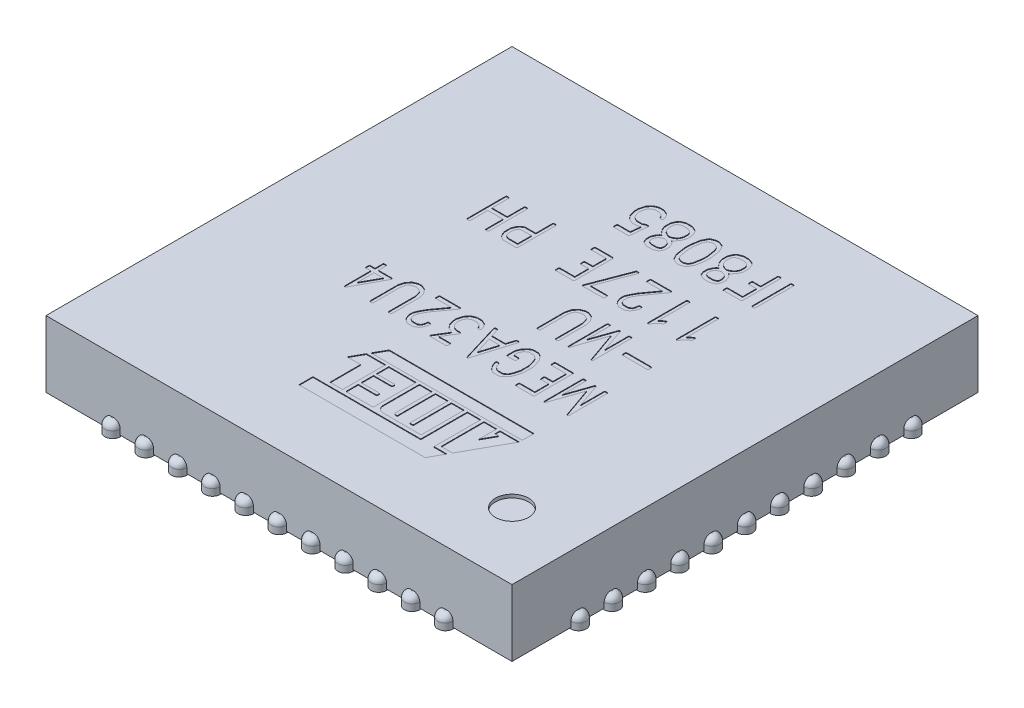
SolidWorks part; units mm, degrees
ref_plane "Front Plane" through (0, 0, 0) normal (0, 0, 1) x (1, 0, 0)
ref_plane "Top Plane" through (0, 0, 0) normal (0, 1, 0) x (1, 0, 0)
ref_plane "Right Plane" through (0, 0, 0) normal (1, 0, 0) x (0, 0, -1)
ref_plane "Plane1" through (0, 0, 0) normal (0, 1, 0) x (-1, 0, 0)
sketch "Sketch1" plane through (0, 0, 0) normal (0, 1, 0) x (-1, 0, 0)
  line L0 (-3.5, 3.5) -> (3.5, 3.5)
  line L1 (3.5, 3.5) -> (3.5, -3.5)
  line L2 (3.5, -3.5) -> (-3.5, -3.5)
  line L3 (-3.5, -3.5) -> (-3.5, 3.5)
  line L4 (55, 0) -> (-55, 0) construction
  line L5 (0, 55) -> (0, -55) construction
  dimension "D1" = 3.5
  dimension "D2" = 7
  dimension "D3" = 3.5
extrude "Boss-Extrude1" add sketch "Sketch1" along normal blind 1
ref_plane "Plane8" through (0, 0, 2.8) normal (0, 0, 1) x (1, 0, 0)
ref_plane "Plane10" through (0, -0.1, 0) normal (0, 1, 0) x (1, 0, 0)
ref_plane "Plane4" through (3.25, 0.6967, 3.35) normal (0, 1, 0) x (0, 0, -1)
ref_plane "Plane9" through (-2.8, 0, 0) normal (1, 0, 0) x (0, 0, -1)
sketch "Sketch4" plane through (0, 1, 0) normal (0, 1, 0) x (1, 0, 0)
  line L2 (3.5, -3.5) -> (3.5, 3.5) construction
  line L3 (-3.5, -3.5) -> (3.5, -3.5) construction
  circle A0 centre (2.5, -2.5) radius 0.25
  dimension "D2" = 0.5
  dimension "D1" = 1
  dimension "D3" = 1
extrude "Cut-Extrude1" cut sketch "Sketch4" against normal blind 0.05
sketch "Sketch8" plane through (0, 1, 0) normal (0, 1, 0) x (1, 0, 0)
  line L0 (-0.5975, -1.59) -> (-0.31, -1.59)
  line L1 (1.7, -1.545) -> (-0.5725, -1.545)
  line L2 (-0.4755, -1.37) -> (-0.5725, -1.545)
  line L3 (-0.26, -1.775) -> (0.005, -1.775)
  line L4 (-0.7, -1.775) -> (-0.5, -1.775)
  line L5 (-0.26, -1.82) -> (0.005, -1.82)
  line L6 (-0.26, -2.005) -> (0.005, -2.005)
  line L7 (-0.26, -2.05) -> (0.005, -2.05)
  line L8 (-0.7, -2.29) -> (0.92, -2.29)
  line L10 (-0.7, -2.5) -> (1.1956, -2.5)
  line L11 (1.7, -1.59) -> (1.3425, -2.235)
  line L12 (0.3, -2.235) -> (0.87, -2.235)
  line L13 (1.41, -1.59) -> (1.41, -1.665)
  line L14 (-0.4755, -1.37) -> (1.7, -1.37)
  line L15 (1.7, -1.37) -> (1.7, -1.545)
  line L16 (1.41, -1.665) -> (1.465, -1.665)
  line L17 (1.465, -1.665) -> (1.36, -1.8544)
  line L18 (1.36, -1.8544) -> (1.36, -1.59)
  line L21 (-0.31, -1.59) -> (-0.31, -2.235)
  line L22 (-0.26, -1.59) -> (-0.26, -2.235)
  line L23 (0.15, -1.59) -> (0.15, -2.235)
  line L24 (0.2, -1.59) -> (0.2, -2.135)
  line L25 (0.39, -1.59) -> (0.39, -2.135)
  line L26 (0.44, -1.59) -> (0.44, -2.165)
  line L27 (0.63, -1.59) -> (0.63, -2.155)
  line L28 (0.68, -1.59) -> (0.68, -2.155)
  line L29 (0.87, -1.59) -> (0.87, -2.235)
  line L30 (0.92, -1.59) -> (0.92, -2.29)
  line L31 (1.12, -1.59) -> (1.12, -2.29)
  line L32 (1.17, -1.59) -> (1.17, -2.235)
  line L33 (0.67, -2.165) -> (0.64, -2.165)
  line L34 (0.44, -2.165) -> (0.42, -2.165)
  line L35 (0.15, -2.235) -> (-0.26, -2.235)
  line L36 (-0.5, -1.775) -> (-0.5, -2.235)
  line L37 (-0.5975, -1.59) -> (-0.7, -1.775)
  line L38 (0.02, -1.79) -> (0.02, -1.805)
  line L39 (1.17, -2.235) -> (1.3425, -2.235)
  line L40 (1.12, -2.29) -> (1.312, -2.29)
  line L41 (-0.26, -1.59) -> (0.15, -1.59)
  line L42 (0.2, -1.59) -> (0.39, -1.59)
  line L43 (0.02, -2.02) -> (0.02, -2.035)
  line L45 (-0.31, -2.235) -> (-0.5, -2.235)
  line L46 (-0.7, -2.29) -> (-0.7, -2.5)
  line L47 (1.312, -2.29) -> (1.1956, -2.5)
  line L48 (0.44, -1.59) -> (0.63, -1.59)
  line L49 (0.68, -1.59) -> (0.87, -1.59)
  line L50 (0.92, -1.59) -> (1.12, -1.59)
  line L51 (1.17, -1.59) -> (1.36, -1.59)
  line L52 (1.41, -1.59) -> (1.7, -1.59)
  line L53 (3.5, -3.5) -> (3.5, 3.5) construction
  line L54 (-3.5, -3.5) -> (3.5, -3.5) construction
  arc A0 (0.3, -2.235) -> (0.2, -2.135) centre (0.3, -2.135) cw
  arc A1 (0.42, -2.165) -> (0.39, -2.135) centre (0.42, -2.135) cw
  arc A2 (0.67, -2.165) -> (0.68, -2.155) centre (0.67, -2.155) ccw
  arc A3 (0.63, -2.155) -> (0.64, -2.165) centre (0.64, -2.155) ccw
  arc A4 (0.005, -2.05) -> (0.02, -2.035) centre (0.005, -2.035) ccw
  arc A5 (0.02, -2.02) -> (0.005, -2.005) centre (0.005, -2.02) ccw
  arc A6 (0.005, -1.82) -> (0.02, -1.805) centre (0.005, -1.805) ccw
  arc A7 (0.02, -1.79) -> (0.005, -1.775) centre (0.005, -1.79) ccw
  point P76 (0.02, -2.005)
  dimension "D28" = 0.1
  dimension "D29" = 0.03
  dimension "D31" = 0.01
  dimension "D36" = 0.015
  dimension "D1" = 0.045
  dimension "D2" = 0.045
  dimension "D3" = 0.045
  dimension "D4" = 0.055
  dimension "D5" = 61
  dimension "D6" = 0.075
  dimension "D7" = 0.055
  dimension "D8" = 1.8
  dimension "D9" = 0.175
  dimension "D10" = 0.185
  dimension "D11" = 0.185
  dimension "D12" = 0.185
  dimension "D13" = 0.21
  dimension "D14" = 0.05
  dimension "D15" = 0.05
  dimension "D16" = 0.05
  dimension "D17" = 0.05
  dimension "D18" = 0.05
  dimension "D19" = 0.05
  dimension "D20" = 0.53
  dimension "D21" = 0.2
  dimension "D22" = 0.19
  dimension "D23" = 0.19
  dimension "D24" = 0.19
  dimension "D25" = 0.41
  dimension "D26" = 2.4
  dimension "D27" = 1
  dimension "D30" = 0.07
  dimension "D32" = 0.19
  dimension "D33" = 0.19
  dimension "D34" = 0.05
  dimension "D35" = 0.28
  dimension "D37" = 1.13
extrude "Cut-Extrude3" cut sketch "Sketch8" against normal blind 0.01 contours L15 L14 L2 L1 | A3 L27 L48 L26 L34 A1 L25 L42 L24 A0 L12 L29 L49 L28 A2 L33 | L50 L30 L8 L46 L10 L47 L40 L31 | L52 L13 L16 L17 L18 L51 L32 L39 L11 | A7 L38 A6 L5 L22 L6 A5 L43 A4 L7 L35 L23 L41 L3 | L45 L21 L0 L37 L4 L36 region at (-0.4366, 1, 1.8723) region at (0.5878, 1, 1.4581) region at (-0.0481, 1, 1.9125) region at (0.11, 1, 2.3121) region at (1.3588, 1, 1.8679) region at (0.5367, 1, 1.9163)
sketch "Sketch9" plane through (0, 1, 0) normal (0, 1, 0) x (1, 0, 0)
  line L0 (1.8, -0.3) -> (-1.8, -0.3) construction
  line L2 (0, -0.561) -> (0, 0.561) construction
  line L3 (-0.561, 0) -> (0.561, 0) construction
  text T0 "MEGA32U4\r\n" font "SWRomnd" height 0.6
  dimension "D1" = 1.8
  dimension "D2" = 0.3
  dimension "D3" = 3.6
extrude "Cut-Extrude6" cut sketch "Sketch9" against normal blind 0.01
sketch "Sketch10" plane through (0, 1, 0) normal (0, 1, 0) x (1, 0, 0)
  line L0 (1.8, 0.6) -> (-0.7662, 0.6) construction
  line L2 (-0.55, 0) -> (0.55, 0) construction
  text T0 "-MU" font "SWRomnd" height 0.6
  dimension "D2" = 0.6
  dimension "D4" = 1.8
extrude "Cut-Extrude5" cut sketch "Sketch10" against normal blind 0.01
sketch "Sketch16" plane through (0, 1, 0) normal (0, 1, 0) x (1, 0, 0)
  line L0 (1.8, 1.5) -> (-2.2, 1.5) construction
  text T0 "1127E PH" font "SWRomnd" height 0.6
  dimension "D1" = 1.8
  dimension "D2" = 1.5
  dimension "D3" = 4
sketch "Sketch17" plane through (0, 1, 0) normal (0, 1, 0) x (1, 0, 0)
  line L0 (-1.8, 2.5) -> (1.8, 2.5) construction
  text T0 "IF8085" font "SWRomnd" height 0.6
  dimension "D1" = 3.6
  dimension "D2" = 1.8
  dimension "D3" = 2.5
extrude "Cut-Extrude9" cut sketch "Sketch16" against normal blind 0.01
extrude "Cut-Extrude10" cut sketch "Sketch17" against normal blind 0.01
sketch "Sketch11" plane through (0, 0, 0) normal (0, -1, 0) x (1, 0, 0)
  line L0 (2.6, 2.6) -> (-2.6, -2.6) construction
  line L1 (-2.6, 2.6) -> (2.6, 2.6)
  line L2 (-2.6, 2.6) -> (-2.6, -2.6)
  line L3 (-2.6, -2.6) -> (2.6, -2.6)
  line L4 (2.6, 2.6) -> (2.6, -2.6)
  dimension "D1" = 5.2
extrude "Boss-Extrude2" add sketch "Sketch11" along normal blind 0.02
sketch "Sketch12" plane through (0, -0.02, 0) normal (0, -1, 0) x (1, 0, 0)
  line L0 (-2.5, 3.5) -> (-2.5, 3.065) construction
  line L1 (-3.5, 3.5) -> (3.5, 3.5) construction
  line L2 (-2.385, 3.5) -> (-2.385, 3.065)
  line L3 (-2.615, 3.5) -> (-2.615, 3.065)
  line L5 (2.6, 2.6) -> (-2.6, 2.6) construction
  line L6 (-2.5, -3.065) -> (-2.5, -3.5) construction
  line L7 (3.5, -3.5) -> (-3.5, -3.5) construction
  line L8 (-2.385, -3.065) -> (-2.385, -3.5)
  line L9 (-2.615, -3.065) -> (-2.615, -3.5)
  arc A0 (-2.385, 3.5) -> (-2.615, 3.5) centre (-2.5, 3.5) ccw
  arc A1 (-2.615, 3.065) -> (-2.385, 3.065) centre (-2.5, 3.065) ccw
  arc A2 (-2.385, -3.065) -> (-2.615, -3.065) centre (-2.5, -3.065) ccw
  arc A3 (-2.615, -3.5) -> (-2.385, -3.5) centre (-2.5, -3.5) ccw
  point P4 (-2.5, 3.2825)
  point P16 (-2.5, -3.2825)
  dimension "D3" = 0.465
  dimension "D1" = 0.23
  dimension "D2" = 2.5
sketch "Sketch13" plane through (0, -0.02, 0) normal (0, -1, 0) x (1, 0, 0)
  line L0 (-3.065, 2.5) -> (-3.5, 2.5) construction
  line L1 (-3.5, -3.5) -> (-3.5, 3.5) construction
  line L2 (-3.065, 2.385) -> (-3.5, 2.385)
  line L3 (-3.065, 2.615) -> (-3.5, 2.615)
  line L4 (3.5, 2.5) -> (3.065, 2.5) construction
  line L5 (3.5, 3.5) -> (3.5, -3.5) construction
  line L6 (3.5, 2.385) -> (3.065, 2.385)
  line L7 (3.5, 2.615) -> (3.065, 2.615)
  line L9 (-2.6, 2.6) -> (-2.6, -2.6) construction
  arc A0 (-3.065, 2.385) -> (-3.065, 2.615) centre (-3.065, 2.5) ccw
  arc A1 (-3.5, 2.615) -> (-3.5, 2.385) centre (-3.5, 2.5) ccw
  arc A2 (3.5, 2.385) -> (3.5, 2.615) centre (3.5, 2.5) ccw
  arc A3 (3.065, 2.615) -> (3.065, 2.385) centre (3.065, 2.5) ccw
  point P4 (-3.2825, 2.5)
  point P9 (3.2825, 2.5)
  dimension "D3" = 0.465
  dimension "D1" = 2.5
  dimension "D2" = 0.23
extrude "Boss-Extrude3" add sketch "Sketch13" against normal blind 0.2
extrude "Boss-Extrude4" add sketch "Sketch12" against normal blind 0.2
fillet "Fillet1" radius 0.1 2 edges at (-2.5, 0.18, -3.615) (-2.5, 0.18, 3.615)
fillet "Fillet2" radius 0.1 2 edges at (3.615, 0.18, 2.5) (-3.615, 0.18, 2.5)
pattern_linear "LPattern3" count 11 spacing 0.5 along (1, 0, 0) of "Boss-Extrude4", "Fillet1"
pattern_linear "LPattern4" count 11 spacing 0.5 along (0, 0, -1) of "Fillet2", "Boss-Extrude3"
chamfer "Chamfer1" distance 0.3 angle 45 1 edges at (2.6, -0.01, 2.6)
ref_axis "Axis1" through (0, 1.051, 0) along (0, -1, 0)
